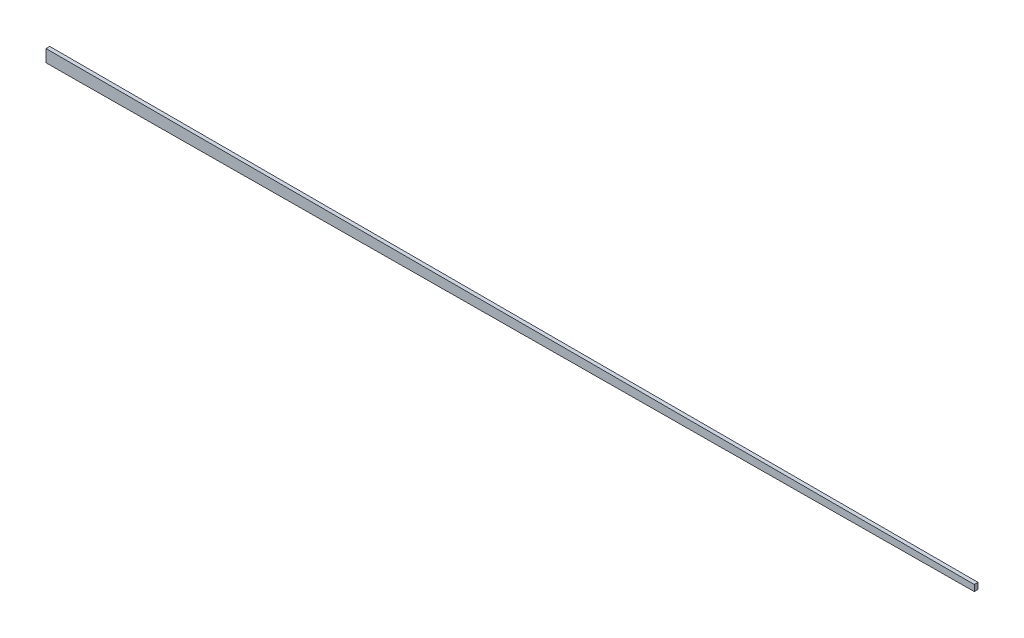
SolidWorks part; units mm, degrees
ref_plane "Front Plane" through (0, 0, 0) normal (0, 0, 1) x (1, 0, 0)
ref_plane "Top Plane" through (0, 0, 0) normal (0, 1, 0) x (1, 0, 0)
ref_plane "Right Plane" through (0, 0, 0) normal (1, 0, 0) x (0, 0, -1)
sketch "Sketch1" plane through (0, 0, 0) normal (0, 0, 1) x (1, 0, 0)
  line L0 (0, 0) -> (750, 5)
  line L1 (750, 5) -> (750, 10)
  line L2 (750, 10) -> (0, 10)
  line L3 (0, 10) -> (0, 0)
  dimension "D1" = 750
  dimension "D2" = 10
  dimension "D3" = 5
extrude "Boss-Extrude1" add sketch "Sketch1" along normal blind 3 contours L0 L1 L2 L3
